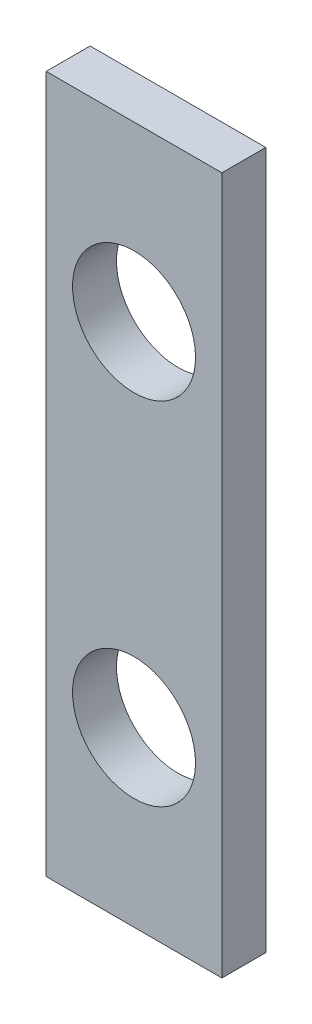
SolidWorks part; units mm, degrees
ref_plane "Front Plane" through (0, 0, 0) normal (0, 0, 1) x (1, 0, 0)
ref_plane "Top Plane" through (0, 0, 0) normal (0, 1, 0) x (1, 0, 0)
ref_plane "Right Plane" through (0, 0, 0) normal (1, 0, 0) x (0, 0, -1)
sketch "Sketch3" plane through (0, 0, 0) normal (0, 1, 0) x (1, 0, 0)
  line L0 (6.282, 2.5073) -> (-1.718, 2.5073)
  line L1 (6.282, 2.5073) -> (6.282, 4.5073)
  line L2 (-1.718, 2.5073) -> (-1.718, 4.5073)
  line L3 (6.282, 4.5073) -> (-1.718, 4.5073)
  line L4 (6.282, 2.5073) -> (-1.718, 4.5073) construction
  line L5 (-1.718, 2.5073) -> (6.282, 4.5073) construction
  point P1 (2.282, 3.5073)
  dimension "D1" = 2
  dimension "D2" = 8
extrude "Boss-Extrude2" add sketch "Sketch3" along normal blind 31.75 separate body
sketch "Sketch4" plane through (0, 0, -2.5073) normal (0, 0, 1) x (1, 0, 0)
  circle A15 centre (2.282, 7.875) radius 2.8
  circle A16 centre (2.282, 23.875) radius 2.8
extrude "Cut-Extrude1" cut sketch "Sketch4" against normal through all
